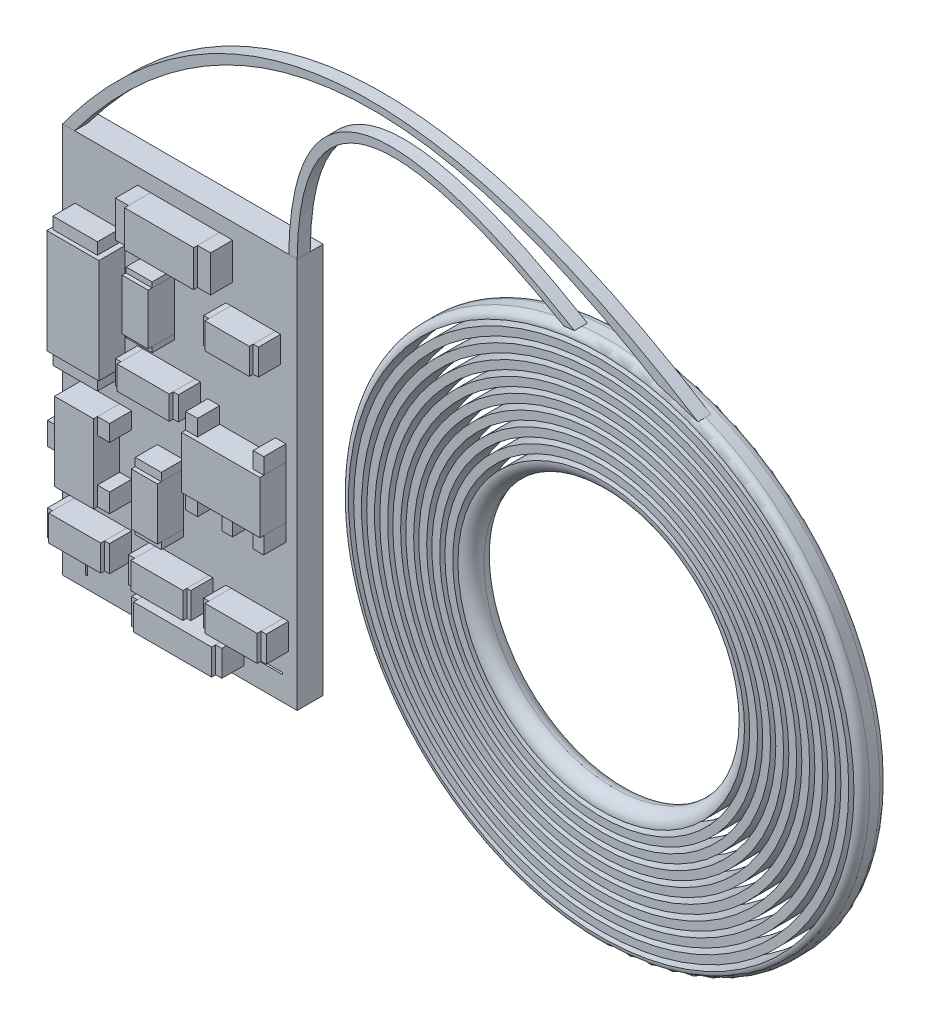
SolidWorks part; units mm, degrees
ref_plane "前视基准面" through (0, 0, 0) normal (0, 0, 1) x (1, 0, 0)
ref_plane "上视基准面" through (0, 0, 0) normal (0, 1, 0) x (1, 0, 0)
ref_plane "右视基准面" through (0, 0, 0) normal (1, 0, 0) x (0, 0, -1)
sketch "草图1" plane through (0, 0, 0) normal (0, 0, 1) x (1, 0, 0)
  circle A0 centre (0, 0) radius 10
  circle A1 centre (0, 0) radius 5
extrude "凸台-拉伸1" add sketch "草图1" along normal blind 1
sketch "草图2" plane through (0, 0, 1) normal (0, 0, 1) x (1, 0, 0)
  circle A0 centre (0, 0) radius 5.5
  circle A1 centre (0, 0) radius 5.7
extrude "切除-拉伸1" cut sketch "草图2" against normal through all contours A1 A0 region at (-5.5388, 0, 1)
sketch "草图4" plane through (0, 0, 1) normal (0, 0, 1) x (1, 0, 0)
  circle A0 centre (0, 0) radius 6
  circle A1 centre (0, 0) radius 6.2
  circle A2 centre (0, 0) radius 6.5
  circle A4 centre (0, 0) radius 6.7
  circle A5 centre (0, 0) radius 7
  circle A6 centre (0, 0) radius 7.2
  circle A7 centre (0, 0) radius 7.5
  circle A8 centre (0, 0) radius 7.7
  circle A9 centre (0, 0) radius 8
  circle A10 centre (0, 0) radius 8.2
  circle A11 centre (0, 0) radius 8.5
  circle A12 centre (0, 0) radius 8.7
  circle A13 centre (0, 0) radius 9
  circle A14 centre (0, 0) radius 9.2
  circle A15 centre (0, 0) radius 9.5
  circle A16 centre (0, 0) radius 9.7
extrude "切除-拉伸2" cut sketch "草图4" against normal through all contours A16 A15 | A14 A13 | A12 A11 | A10 A9 | A8 A7 | A6 A5 | A4 A2 | A1 A0 region at (-6.0246, 0, 1) region at (-6.5105, 0, 1) region at (-7.1796, 0, 1) region at (-7.6782, 0, 1) region at (-8.1768, 0, 1) region at (-8.6754, 0, 1) region at (-9.174, 0, 1) region at (-9.6726, 0, 1)
fillet "圆角1" radius 0.5 2 edges at (5, 0, 0) (5, 0, 1)
fillet "圆角2" radius 0.3 2 edges at (10, 0, 1) (10, 0, 0)
sketch "草图5" plane through (0, 0, 0) normal (0, 0, 1) x (1, 0, 0)
  line L0 (0, 0) -> (-11.67, 0) construction
  line L1 (-11.67, 0) -> (-11.67, 7)
  line L2 (-11.67, 7) -> (-20.67, 7)
  line L3 (-20.67, 7) -> (-20.67, -8)
  line L4 (-20.67, -8) -> (-11.67, -8)
  line L5 (-11.67, -8) -> (-11.67, 0)
extrude "凸台-拉伸2" add sketch "草图5" along normal blind 1 separate body
sketch "草图6" plane through (0, 0, 1) normal (0, 0, 1) x (1, 0, 0)
  line L0 (-11.67, 7) -> (-20.67, 7) construction
  line L1 (-1.4265, 9.8977) -> (-1.0295, 9.9469)
  line L2 (-11.67, 7) -> (-11.9928, 7)
  line L3 (2.1434, 9.7676) -> (3.7117, 9.2857)
  line L4 (-20.2111, 7) -> (-20.67, 7)
  circle A0 centre (0, 0) radius 10 construction
  spline S0 degree 2 poles (-11.67, 7) (-11.5921, 15.7474) (-1.4265, 9.8977) knots 0 0 0 1 1 1
  spline S1 degree 2 poles (-11.9928, 7) (-11.8384, 16.3442) (-1.0295, 9.9469) knots 0 0 0 1 1 1
  spline S2 degree 2 poles (-20.67, 7) (-11.8691, 19.0966) (3.7117, 9.2857) knots 0 0 0 1 1 1
  spline S3 degree 2 poles (-20.2111, 7) (-11.7055, 18.2551) (2.1434, 9.7676) knots 0 0 0 1 1 1
extrude "凸台-拉伸3" add sketch "草图6" against normal blind 0.5 separate body
sketch "草图7" plane through (0, 0, 1) normal (0, 0, 1) x (1, 0, 0)
  line L0 (-11.67, -6.5561) -> (-13.7745, -6.5561) construction
  line L1 (-11.67, -8) -> (-11.67, 7) construction
  line L3 (-20.67, 7) -> (-20.67, -8) construction
  line L4 (-20.67, -6.5561) -> (-18.8339, -6.5561) construction
  text T0 "-" font "汉仪长仿宋体" height in points 4
  text T1 "+" font "汉仪长仿宋体" height in points 4
extrude "切除-拉伸3" cut sketch "草图7" against normal blind 0.1
sketch "草图8" plane through (0, 0, 1) normal (0, 0, 1) x (1, 0, 0)
  line L1 (-17.2925, 6.3986) -> (-14.643, 6.3986)
  line L2 (-17.2925, 6.3986) -> (-17.2925, 4.9989)
  line L3 (-17.2925, 4.9989) -> (-14.643, 4.9989)
  line L4 (-14.643, 6.3986) -> (-14.643, 4.9989)
  line L5 (-14.2058, 4.1854) -> (-12.5061, 4.1854)
  line L6 (-14.2058, 4.1854) -> (-14.2058, 3.1854)
  line L7 (-14.2058, 3.1854) -> (-12.5061, 3.1854)
  line L8 (-12.5061, 4.1854) -> (-12.5061, 3.1854)
  line L13 (-15.1001, 0.0293) -> (-12.1001, 0.0293)
  line L14 (-15.1001, 0.0293) -> (-15.1001, -1.9707)
  line L15 (-15.1001, -1.9707) -> (-12.1001, -1.9707)
  line L16 (-12.1001, 0.0293) -> (-12.1001, -1.9707)
  line L17 (-17.3849, 4.113) -> (-16.3849, 4.113)
  line L18 (-17.3849, 4.113) -> (-17.3849, 2.1606)
  line L19 (-17.3849, 2.1606) -> (-16.3849, 2.1606)
  line L20 (-16.3849, 4.113) -> (-16.3849, 2.1606)
  line L21 (-20.2798, 4.1497) -> (-18.2798, 4.1497)
  line L22 (-20.2798, 4.1497) -> (-20.2798, 0.1497)
  line L23 (-20.2798, 0.1497) -> (-18.2798, 0.1497)
  line L24 (-18.2798, 4.1497) -> (-18.2798, 0.1497)
  line L25 (-17.5802, 1.0635) -> (-15.5802, 1.0635)
  line L26 (-17.5802, 1.0635) -> (-17.5802, 0.1571)
  line L27 (-17.5802, 0.1571) -> (-15.5802, 0.1571)
  line L28 (-15.5802, 1.0635) -> (-15.5802, 0.1571)
  line L29 (-17.0336, -2.1507) -> (-16.0336, -2.1507)
  line L30 (-17.0336, -2.1507) -> (-17.0336, -4.1507)
  line L31 (-17.0336, -4.1507) -> (-16.0336, -4.1507)
  line L32 (-16.0336, -2.1507) -> (-16.0336, -4.1507)
  line L33 (-19.9834, -1.2105) -> (-18.4834, -1.2105)
  line L34 (-19.9834, -1.2105) -> (-19.9834, -4.2105)
  line L35 (-19.9834, -4.2105) -> (-18.4834, -4.2105)
  line L36 (-18.4834, -1.2105) -> (-18.4834, -4.2105) construction
  line L37 (-16.9514, -6.5319) -> (-13.9514, -6.5319)
  line L38 (-16.9514, -6.5319) -> (-16.9514, -7.5319)
  line L39 (-16.9514, -7.5319) -> (-13.9514, -7.5319)
  line L40 (-13.9514, -6.5319) -> (-13.9514, -7.5319)
  line L41 (-20.2081, -5.2036) -> (-18.2081, -5.2036)
  line L42 (-20.2081, -5.2036) -> (-20.2081, -6.2036)
  line L43 (-20.2081, -6.2036) -> (-18.2081, -6.2036)
  line L44 (-18.2081, -5.2036) -> (-18.2081, -6.2036)
  line L45 (-17.0534, -5.2036) -> (-15.0534, -5.2036)
  line L46 (-17.0534, -5.2036) -> (-17.0534, -6.2036)
  line L47 (-17.0534, -6.2036) -> (-15.0534, -6.2036)
  line L48 (-15.0534, -5.2036) -> (-15.0534, -6.2036)
  line L49 (-14.2058, -5.2036) -> (-12.2058, -5.2036)
  line L50 (-14.2058, -5.2036) -> (-14.2058, -6.2036)
  line L51 (-14.2058, -6.2036) -> (-12.2058, -6.2036)
  line L52 (-12.2058, -5.2036) -> (-12.2058, -6.2036)
extrude "凸台-拉伸4" add sketch "草图8" along normal blind 1 contours L24 L21 L22 L23 | L20 L17 L18 L19 | L8 L5 L6 L7 | L16 L13 L14 L15 | L28 L25 L26 L27 | L32 L29 L30 L31 | L36 L33 L34 L35 | L48 L45 L46 L47 | L52 L49 L50 L51 | L40 L37 L38 L39 | L44 L41 L42 L43 | L4 L1 L2 L3
sketch "草图9" plane through (0, 0, 1) normal (0, 0, 1) x (1, 0, 0)
  line L0 (-15.1001, -1.9707) -> (-12.1001, -1.9707) construction
  line L1 (-14.643, 6.3986) -> (-14.143, 6.3986)
  line L2 (-14.643, 6.3986) -> (-14.643, 4.9989)
  line L3 (-14.643, 4.9989) -> (-14.143, 4.9989)
  line L4 (-14.143, 6.3986) -> (-14.143, 4.9989)
  line L5 (-17.2925, 6.3986) -> (-17.7925, 6.3986)
  line L6 (-17.2925, 6.3986) -> (-17.2925, 4.9989)
  line L7 (-17.2925, 4.9989) -> (-17.7925, 4.9989)
  line L8 (-17.7925, 6.3986) -> (-17.7925, 4.9989)
  line L9 (-14.2058, 4.1854) -> (-14.4058, 4.1854)
  line L10 (-14.2058, 4.1854) -> (-14.2058, 3.1854)
  line L11 (-14.2058, 3.1854) -> (-14.4058, 3.1854)
  line L12 (-14.4058, 4.1854) -> (-14.4058, 3.1854)
  line L13 (-12.5061, 4.1854) -> (-12.3061, 4.1854)
  line L14 (-12.5061, 4.1854) -> (-12.5061, 3.1854)
  line L15 (-12.5061, 3.1854) -> (-12.3061, 3.1854)
  line L16 (-12.3061, 4.1854) -> (-12.3061, 3.1854)
  line L17 (-17.3849, 4.113) -> (-16.3849, 4.113)
  line L18 (-17.3849, 4.113) -> (-17.3849, 4.313)
  line L19 (-17.3849, 4.313) -> (-16.3849, 4.313)
  line L20 (-16.3849, 4.113) -> (-16.3849, 4.313)
  line L21 (-17.3849, 2.1606) -> (-16.3849, 2.1606)
  line L22 (-17.3849, 2.1606) -> (-17.3849, 1.9606)
  line L23 (-17.3849, 1.9606) -> (-16.3849, 1.9606)
  line L24 (-16.3849, 2.1606) -> (-16.3849, 1.9606)
  line L25 (-15.5802, 1.0635) -> (-15.3802, 1.0635)
  line L26 (-15.5802, 1.0635) -> (-15.5802, 0.1571)
  line L27 (-15.5802, 0.1571) -> (-15.3802, 0.1571)
  line L28 (-15.3802, 1.0635) -> (-15.3802, 0.1571)
  line L29 (-17.5802, 1.0635) -> (-17.7925, 1.0635)
  line L30 (-17.5802, 1.0635) -> (-17.5802, 0.1571)
  line L31 (-17.5802, 0.1571) -> (-17.7925, 0.1571)
  line L32 (-17.7925, 1.0635) -> (-17.7925, 0.1571)
  line L33 (-17.0336, -2.1507) -> (-16.0336, -2.1507)
  line L34 (-17.0336, -2.1507) -> (-17.0336, -1.8412)
  line L35 (-17.0336, -1.8412) -> (-16.0336, -1.8412)
  line L36 (-16.0336, -2.1507) -> (-16.0336, -1.8412)
  line L37 (-16.0336, -4.1507) -> (-17.0336, -4.1507)
  line L38 (-16.0336, -4.1507) -> (-16.0336, -4.413)
  line L39 (-16.0336, -4.413) -> (-17.0336, -4.413)
  line L40 (-17.0336, -4.1507) -> (-17.0336, -4.413)
  line L41 (-18.2081, -5.2036) -> (-18.0197, -5.2036)
  line L42 (-18.2081, -5.2036) -> (-18.2081, -6.2036)
  line L43 (-18.2081, -6.2036) -> (-18.0197, -6.2036)
  line L44 (-18.0197, -5.2036) -> (-18.0197, -6.2036)
  line L45 (-20.2081, -5.2036) -> (-20.4019, -5.2036)
  line L46 (-20.2081, -5.2036) -> (-20.2081, -6.2036)
  line L47 (-20.2081, -6.2036) -> (-20.4019, -6.2036)
  line L48 (-20.4019, -5.2036) -> (-20.4019, -6.2036)
  line L49 (-17.0534, -5.2036) -> (-17.2925, -5.2036)
  line L50 (-17.0534, -5.2036) -> (-17.0534, -6.2036)
  line L51 (-17.0534, -6.2036) -> (-17.2925, -6.2036)
  line L52 (-17.2925, -5.2036) -> (-17.2925, -6.2036)
  line L53 (-15.0534, -5.2036) -> (-14.903, -5.2036)
  line L54 (-15.0534, -5.2036) -> (-15.0534, -6.2036)
  line L55 (-15.0534, -6.2036) -> (-14.903, -6.2036)
  line L56 (-14.903, -5.2036) -> (-14.903, -6.2036)
  line L57 (-14.2058, -5.2036) -> (-14.4058, -5.2036)
  line L58 (-14.2058, -5.2036) -> (-14.2058, -6.2036)
  line L59 (-14.2058, -6.2036) -> (-14.4058, -6.2036)
  line L60 (-14.4058, -5.2036) -> (-14.4058, -6.2036)
  line L61 (-12.2058, -5.2036) -> (-12.0046, -5.2036)
  line L62 (-12.2058, -5.2036) -> (-12.2058, -6.2036)
  line L63 (-12.2058, -6.2036) -> (-12.0046, -6.2036)
  line L64 (-12.0046, -5.2036) -> (-12.0046, -6.2036)
  line L65 (-13.9514, -6.5319) -> (-13.7118, -6.5319)
  line L66 (-13.9514, -6.5319) -> (-13.9514, -7.5267)
  line L67 (-13.9514, -7.5267) -> (-13.7118, -7.5267)
  line L68 (-13.7118, -6.5319) -> (-13.7118, -7.5267)
  line L69 (-16.9514, -6.5319) -> (-17.173, -6.5319)
  line L70 (-16.9514, -6.5319) -> (-16.9514, -7.5267)
  line L71 (-16.9514, -7.5267) -> (-17.173, -7.5267)
  line L72 (-17.173, -6.5319) -> (-17.173, -7.5267)
  line L73 (-15.1001, 0.0293) -> (-14.643, 0.0293)
  line L74 (-15.1001, 0.0293) -> (-15.1001, 0.648)
  line L75 (-15.1001, 0.648) -> (-14.643, 0.648)
  line L76 (-14.643, 0.0293) -> (-14.643, 0.648)
  line L77 (-12.1001, 0.0293) -> (-12.5061, 0.0293)
  line L78 (-12.1001, 0.0293) -> (-12.1001, 0.648)
  line L79 (-12.1001, 0.648) -> (-12.5061, 0.648)
  line L80 (-12.5061, 0.0293) -> (-12.5061, 0.648)
  line L81 (-15.1001, -1.9707) -> (-14.643, -1.9707)
  line L82 (-15.1001, -1.9707) -> (-15.1001, -2.621)
  line L83 (-15.1001, -2.621) -> (-14.643, -2.621)
  line L84 (-14.643, -1.9707) -> (-14.643, -2.621)
  line L85 (-13.7118, -1.9707) -> (-13.3014, -1.9707)
  line L86 (-13.7118, -1.9707) -> (-13.7118, -2.621)
  line L87 (-13.7118, -2.621) -> (-13.3014, -2.621)
  line L88 (-13.3014, -1.9707) -> (-13.3014, -2.621)
  line L89 (-19.9834, -1.2105) -> (-19.9834, -4.2105) construction
  line L90 (-12.1001, -1.9707) -> (-12.5061, -1.9707)
  line L91 (-12.1001, -1.9707) -> (-12.1001, -2.621)
  line L92 (-12.1001, -2.621) -> (-12.5061, -2.621)
  line L93 (-12.5061, -1.9707) -> (-12.5061, -2.621)
  line L94 (-18.4834, -1.2105) -> (-18.0197, -1.2105)
  line L95 (-18.4834, -1.2105) -> (-18.4834, -1.8412)
  line L96 (-18.4834, -1.8412) -> (-18.0197, -1.8412)
  line L97 (-18.0197, -1.2105) -> (-18.0197, -1.8412)
  line L98 (-18.4834, -4.2105) -> (-18.0197, -4.2105)
  line L99 (-18.4834, -4.2105) -> (-18.4834, -3.4873)
  line L100 (-18.4834, -3.4873) -> (-18.0197, -3.4873)
  line L101 (-18.0197, -4.2105) -> (-18.0197, -3.4873)
  line L102 (-19.9834, -2.2959) -> (-20.4019, -2.2959)
  line L103 (-19.9834, -2.2959) -> (-19.9834, -3.1604)
  line L104 (-19.9834, -3.1604) -> (-20.4019, -3.1604)
  line L105 (-20.4019, -2.2959) -> (-20.4019, -3.1604)
  line L106 (-20.2798, 0.1497) -> (-18.2798, 0.1497) construction
  line L107 (-20.1926, 0.1497) -> (-18.4834, 0.1497)
  line L108 (-20.1926, 0.1497) -> (-20.1926, -0.3668)
  line L109 (-20.1926, -0.3668) -> (-18.4834, -0.3668)
  line L110 (-18.4834, 0.1497) -> (-18.4834, -0.3668)
  line L111 (-20.2798, 4.1497) -> (-18.2798, 4.1497) construction
  line L112 (-20.1926, 4.1497) -> (-18.4834, 4.1497)
  line L113 (-20.1926, 4.1497) -> (-20.1926, 4.5989)
  line L114 (-20.1926, 4.5989) -> (-18.4834, 4.5989)
  line L115 (-18.4834, 4.1497) -> (-18.4834, 4.5989)
extrude "凸台-拉伸5" add sketch "草图9" along normal blind 0.85 separate body contours L5 L8 L7 L6 | L4 L1 L2 L3 | L9 L12 L11 L10 | L16 L13 L14 L15 | L112 L115 L114 L113 | L110 L107 L108 L109 | L73 L76 L75 L74 | L80 L77 L78 L79 | L90 L93 L92 L91 | L88 L85 L86 L87 | L84 L81 L82 L83 | L33 L36 L35 L34 | L37 L40 L39 L38 | L97 L94 L95 L96 | L102 L105 L104 L103 | L98 L101 L100 L99 | L45 L48 L47 L46 | L44 L41 L42 L43 | L68 L65 L66 L67 | L69 L72 L71 L70 | L17 L20 L19 L18 | L21 L24 L23 L22 | L32 L31 L30 L29 | L28 L27 L26 L25 | L52 L51 L50 L49 | L54 L55 L56 L53 | L58 L59 L60 L57 | L62 L63 L64 L61 region at (-14.393, 5.6987, 1) region at (-17.5425, 5.6987, 1) region at (-14.3058, 3.6854, 1) region at (-12.4061, 3.6854, 1) region at (-16.5336, -1.996, 1) region at (-16.5336, -4.2819, 1) region at (-18.1139, -5.7036, 1) region at (-20.305, -5.7036, 1) region at (-13.8316, -7.0293, 1) region at (-17.0622, -7.0293, 1) region at (-14.8716, 0.3387, 1) region at (-12.3031, 0.3387, 1) region at (-14.8716, -2.2959, 1) region at (-13.5066, -2.2959, 1) region at (-12.3031, -2.2959, 1) region at (-18.2515, -1.5259, 1) region at (-18.2515, -3.8489, 1) region at (-20.1926, -2.7282, 1) region at (-19.338, -0.1086, 1) region at (-19.338, 4.3743, 1)
